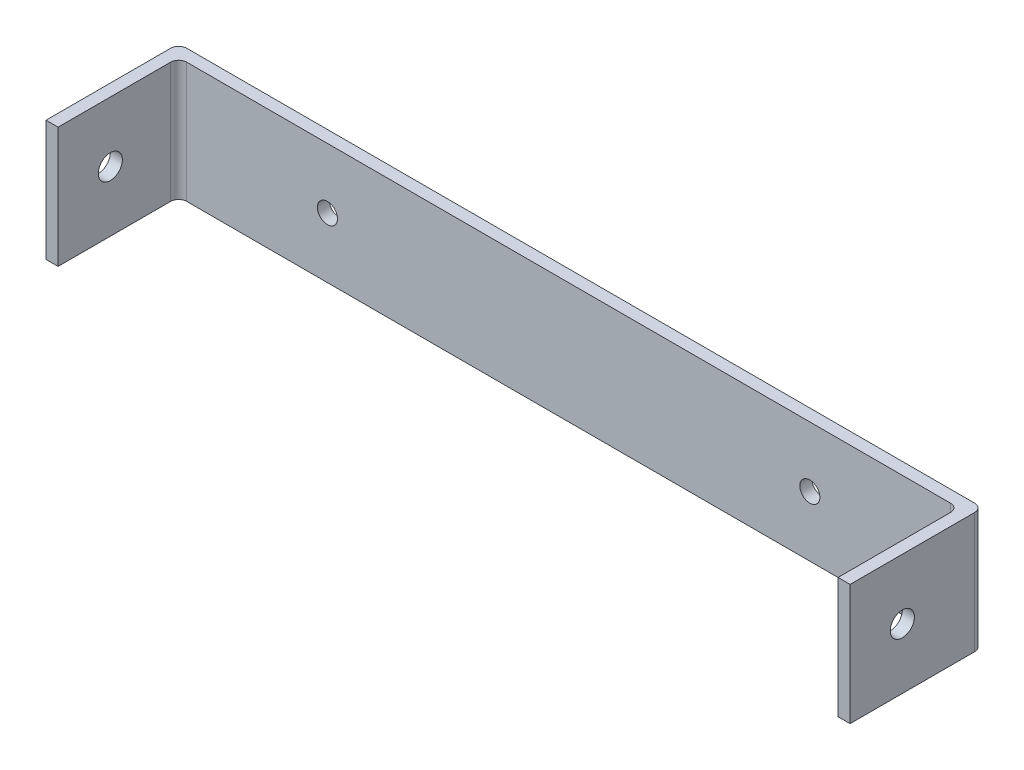
SolidWorks part; units mm, degrees
ref_plane "Plan de face" through (0, 0, 0) normal (0, 0, 1) x (1, 0, 0)
ref_plane "Plan de dessus" through (0, 0, 0) normal (0, 1, 0) x (1, 0, 0)
ref_plane "Plan de droite" through (0, 0, 0) normal (1, 0, 0) x (0, 0, -1)
sketch "Esquisse1" plane through (0, 0, 0) normal (0, 0, 1) x (1, 0, 0)
  line L1 (0, 0) -> (200, 0)
  line L2 (0, 0) -> (0, -30)
  line L3 (0, -30) -> (200, -30)
  line L4 (200, 0) -> (200, -30)
  circle A0 centre (40, -15) radius 2.5
  circle A1 centre (160, -15) radius 2.5
  dimension "D2" = 5
  dimension "D3" = 5
  dimension "D1" = 30
  dimension "D4" = 15
  dimension "D5" = 15
  dimension "D6" = 120
  dimension "D7" = 200
  dimension "D8" = 40
extrude "Boss.-Extru.1" add sketch "Esquisse1" along normal blind 3
sketch "Esquisse2" plane through (0, 0, 3) normal (0, 0, 1) x (1, 0, 0)
  line L0 (200, 0) -> (0, 0) construction
  line L1 (0, -30) -> (3, -30)
  line L2 (0, -30) -> (0, 0)
  line L3 (0, 0) -> (3, 0)
  line L4 (3, -30) -> (3, 0)
  line L5 (0, -30) -> (200, -30) construction
  line L6 (200, 0) -> (197, 0)
  line L7 (200, 0) -> (200, -30)
  line L8 (200, -30) -> (197, -30)
  line L9 (197, 0) -> (197, -30)
  point P14 (200, -15)
  dimension "D1" = 3
  dimension "D2" = 3
extrude "Boss.-Extru.2" add sketch "Esquisse2" along normal blind 30
sketch "Esquisse3" plane through (0, 0, 0) normal (-1, 0, 0) x (0, 0, 1)
  line L0 (33, 0) -> (0, 0) construction
  line L2 (0, 0) -> (0, -30) construction
  circle A0 centre (20, -15) radius 3
  dimension "D1" = 6
  dimension "D2" = 15
  dimension "D3" = 20
extrude "Enlèv. mat.-Extru.1" cut sketch "Esquisse3" against normal blind 229
fillet "Congé1" radius 2 4 edges at (200, -15, 0) (197, -15, 3) (0, -15, 0) (3, -15, 3)
